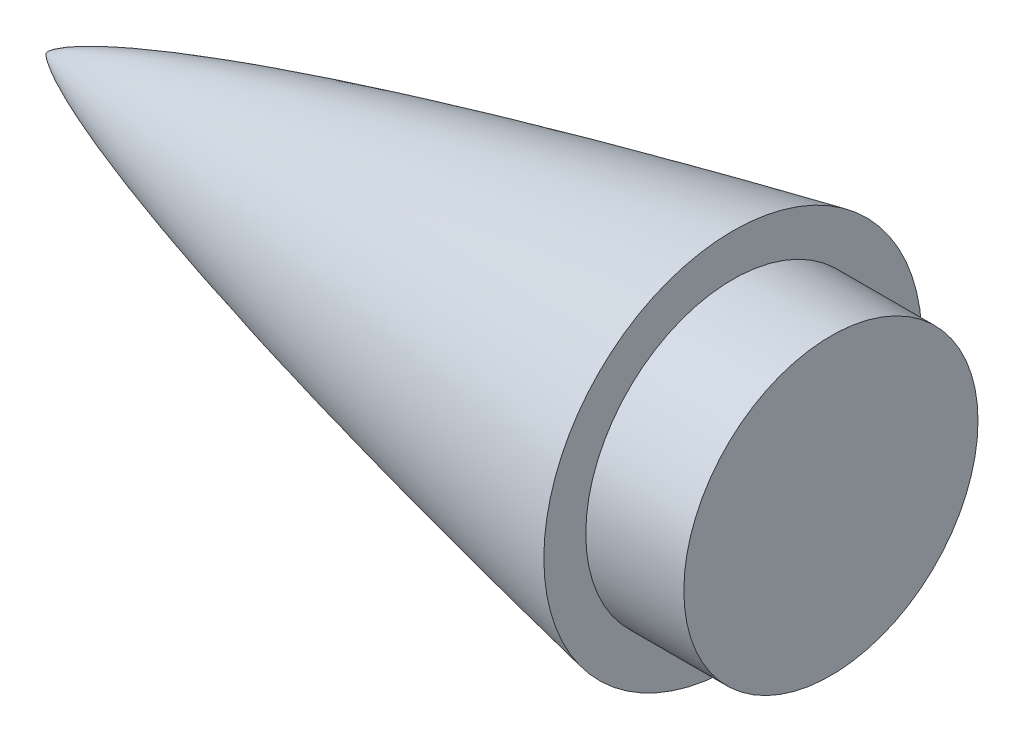
SolidWorks part; units mm, degrees
material "1060 Alloy"
ref_plane "Front Plane" through (0, 0, 0) normal (0, 0, 1) x (1, 0, 0)
ref_plane "Top Plane" through (0, 0, 0) normal (0, 1, 0) x (1, 0, 0)
ref_plane "Right Plane" through (0, 0, 0) normal (1, 0, 0) x (0, 0, -1)
sketch "Sketch1" plane through (0, 0, 0) normal (0, 0, 1) x (1, 0, 0)
  line L0 (0, 0) -> (50.8, 0)
  line L1 (44.45, 9.525) -> (44.45, 12.2404)
  line L2 (44.45, 9.525) -> (50.8, 9.525)
  line L3 (50.8, 9.525) -> (50.8, 0)
  spline S0 degree 4 poles (0, 0) (0.003, 0.0098) (0.0106, 0.0263) (0.0259, 0.0477) (0.0496, 0.0773) (0.0811, 0.1115) (0.1284, 0.1575) (0.2052, 0.2238) (0.3322, 0.3214) (0.5446, 0.4658) (0.9016, 0.6802) (1.5114, 1.0017) (2.4628, 1.4428) (4.093, 2.1112) (6.3816, 2.9359) (9.2264, 3.8553) (12.4937, 4.8221) (15.8352, 5.7433) (19.1577, 6.6111) (22.5404, 7.451) (25.8486, 8.2426) (29.2981, 9.0336) (32.5312, 9.7563) (36.1346, 10.5306) (39.1375, 11.1649) (42.7985, 11.9108) (44.8638, 12.3243) (46.8343, 12.7126) (48.2067, 12.9815) (48.5075, 13.0385) (48.933, 13.1217) knots 0 0 0 0 0 0.000801 0.001434 0.00205 0.002997 0.004453 0.00663 0.010024 0.015611 0.024646 0.039425 0.064225 0.09821 0.163174 0.231144 0.299114 0.367084 0.435053 0.503023 0.570993 0.638963 0.706933 0.774903 0.842873 0.910843 0.955421 0.977711 1 1 1 1 1 construction
  spline S1 degree 4 poles (0, 0) (0.003, 0.0098) (0.0106, 0.0263) (0.0259, 0.0477) (0.0496, 0.0773) (0.0811, 0.1115) (0.1284, 0.1575) (0.2052, 0.2238) (0.3322, 0.3214) (0.5446, 0.4658) (0.9016, 0.6802) (1.5114, 1.0017) (2.4628, 1.4428) (4.093, 2.1112) (6.3816, 2.9359) (9.2264, 3.8553) (12.4937, 4.8221) (15.8352, 5.7433) (19.1577, 6.6111) (22.5404, 7.451) (25.8486, 8.2426) (29.2981, 9.0336) (32.5312, 9.7563) (36.1346, 10.5306) (39.1375, 11.1649) (42.1417, 11.7769) (43.6788, 12.0864) (44.45, 12.2404) knots 0 0 0 0 0 0.000801 0.001434 0.00205 0.002997 0.004453 0.00663 0.010024 0.015611 0.024646 0.039425 0.064225 0.09821 0.163174 0.231144 0.299114 0.367084 0.435053 0.503023 0.570993 0.638963 0.706933 0.774903 0.842873 0.910843 0.910843 0.910843 0.910843 0.910843
  dimension "D1" = 44.45
  dimension "D2" = 9.525
  dimension "D3" = 6.35
revolve "Revolve1" add sketch "Sketch1" angle 360 about L0
ref_axis "Axis1" through (46.6725, 0, 0) along (-1, 0, 0)
